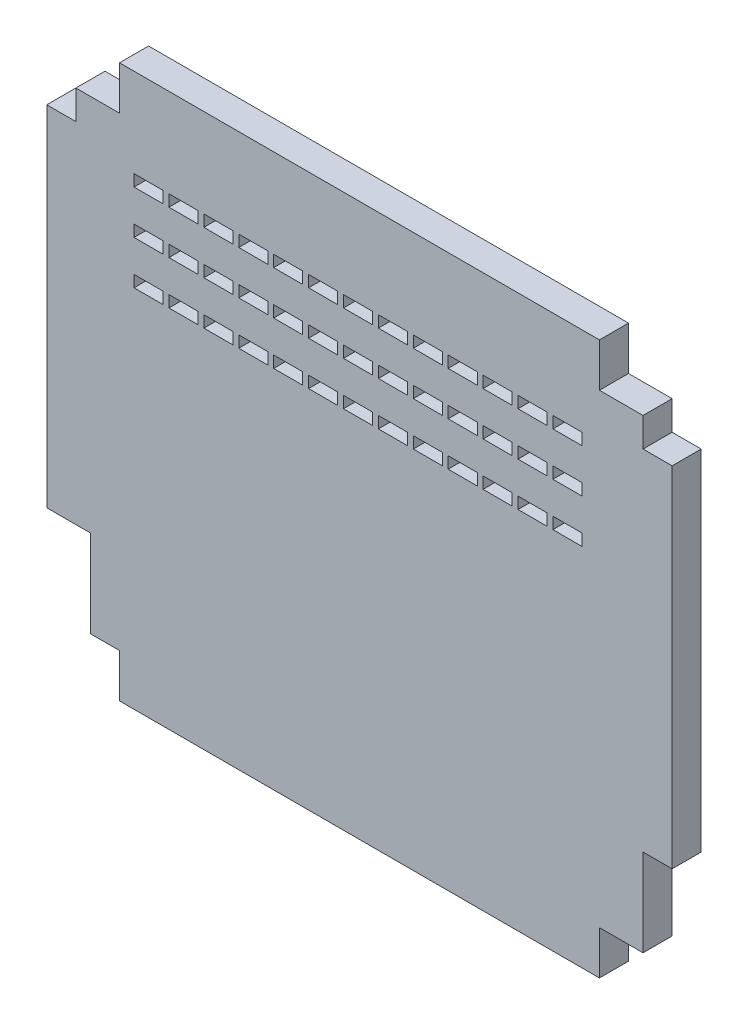
SolidWorks part; units mm, degrees
ref_plane "前视基准面" through (0, 0, 0) normal (0, 0, 1) x (1, 0, 0)
ref_plane "上视基准面" through (0, 0, 0) normal (0, 1, 0) x (1, 0, 0)
ref_plane "右视基准面" through (0, 0, 0) normal (1, 0, 0) x (0, 0, -1)
sketch "草图1" plane through (0, 0, 0) normal (0, 0, 1) x (1, 0, 0)
  line L0 (-82.5, 0) -> (82.5, 0)
  line L2 (107.5, -25) -> (107.5, -145)
  line L3 (-107.5, -25) -> (-107.5, -145)
  line L6 (-82.5, -190) -> (82.5, -190)
  line L8 (-107.5, -25) -> (-97.5, -25)
  line L9 (-97.5, -25) -> (-97.5, -15)
  line L10 (-97.5, -15) -> (-82.5, -15)
  line L11 (-82.5, -15) -> (-82.5, 0)
  line L12 (82.5, 0) -> (82.5, -15)
  line L13 (82.5, -15) -> (97.5, -15)
  line L14 (97.5, -15) -> (97.5, -25)
  line L15 (97.5, -25) -> (107.5, -25)
  line L16 (-107.5, -145) -> (-92.5, -145)
  line L17 (-92.5, -145) -> (-92.5, -175)
  line L18 (-92.5, -175) -> (-82.5, -175)
  line L19 (-82.5, -175) -> (-82.5, -190)
  line L20 (107.5, -145) -> (97.5, -145)
  line L21 (97.5, -145) -> (97.5, -175)
  line L22 (97.5, -175) -> (82.5, -175)
  line L23 (82.5, -175) -> (82.5, -190)
  point P6 (107.5, -85)
  point P9 (-107.5, -85)
  point P11 (0, 0)
  dimension "D1" = 215
  dimension "D2" = 10
  dimension "D3" = 15
  dimension "15" = 15
  dimension "D5" = 10
  dimension "D6" = 15
  dimension "D7" = 15
  dimension "D8" = 120
  dimension "D9" = 30
  dimension "D10" = 30
  dimension "D11" = 15
  dimension "D12" = 10
  dimension "D13" = 15
  dimension "D14" = 10
extrude "凸台-拉伸1" add sketch "草图1" along normal blind 10
sketch "草图2" plane through (0, 0, 0) normal (0, 0, -1) x (-1, 0, 0)
  line L0 (82.5, 0) -> (82.5, -15) construction
  line L161 (-54.5, -5) -> (-54.5, -15)
  line L166 (-54.5, -5) -> (-64.5, -5)
  line L167 (77.5, -5) -> (67.5, -5)
  line L168 (77.5, -5) -> (77.5, -15)
  line L169 (77.5, -15) -> (67.5, -15)
  line L170 (67.5, -5) -> (67.5, -15)
  line L171 (-82.5, 0) -> (82.5, 0) construction
  line L172 (65.5, -5) -> (65.5, -15)
  line L173 (65.5, -5) -> (55.5, -5)
  line L174 (55.5, -5) -> (55.5, -15)
  line L175 (65.5, -15) -> (55.5, -15)
  line L176 (53.5, -5) -> (53.5, -15)
  line L177 (53.5, -5) -> (43.5, -5)
  line L178 (43.5, -5) -> (43.5, -15)
  line L433 (53.5, -15) -> (43.5, -15)
  line L506 (89.5, -20) -> (89.5, -30)
  line L507 (89.5, -30) -> (79.5, -30)
  line L508 (79.5, -20) -> (79.5, -30)
  line L509 (89.5, -20) -> (79.5, -20)
  line L510 (89.5, -35) -> (89.5, -45)
  line L511 (89.5, -45) -> (79.5, -45)
  line L512 (79.5, -35) -> (79.5, -45)
  line L513 (89.5, -35) -> (79.5, -35)
  line L514 (89.5, -50) -> (89.5, -60)
  line L515 (89.5, -60) -> (79.5, -60)
  line L516 (79.5, -50) -> (79.5, -60)
  line L517 (89.5, -50) -> (79.5, -50)
  line L518 (89.5, -65) -> (89.5, -75)
  line L519 (89.5, -75) -> (79.5, -75)
  line L520 (41.5, -5) -> (41.5, -15)
  line L521 (41.5, -5) -> (31.5, -5)
  line L522 (31.5, -5) -> (31.5, -15)
  line L523 (41.5, -15) -> (31.5, -15)
  line L524 (29.5, -5) -> (29.5, -15)
  line L525 (29.5, -5) -> (19.5, -5)
  line L526 (19.5, -5) -> (19.5, -15)
  line L527 (29.5, -15) -> (19.5, -15)
  line L528 (17.5, -5) -> (17.5, -15)
  line L529 (17.5, -5) -> (7.5, -5)
  line L530 (7.5, -5) -> (7.5, -15)
  line L531 (17.5, -15) -> (7.5, -15)
  line L532 (5.5, -5) -> (5.5, -15)
  line L533 (5.5, -5) -> (-4.5, -5)
  line L534 (-4.5, -5) -> (-4.5, -15)
  line L535 (5.5, -15) -> (-4.5, -15)
  line L536 (-6.5, -5) -> (-6.5, -15)
  line L537 (-6.5, -5) -> (-16.5, -5)
  line L538 (-16.5, -5) -> (-16.5, -15)
  line L539 (-6.5, -15) -> (-16.5, -15)
  line L540 (-18.5, -5) -> (-18.5, -15)
  line L541 (-18.5, -5) -> (-28.5, -5)
  line L542 (-28.5, -5) -> (-28.5, -15)
  line L543 (-18.5, -15) -> (-28.5, -15)
  line L544 (-30.5, -5) -> (-30.5, -15)
  line L545 (-30.5, -5) -> (-40.5, -5)
  line L546 (-40.5, -5) -> (-40.5, -15)
  line L547 (-30.5, -15) -> (-40.5, -15)
  line L548 (-42.5, -5) -> (-42.5, -15)
  line L549 (-42.5, -5) -> (-52.5, -5)
  line L550 (-52.5, -5) -> (-52.5, -15)
  line L551 (-42.5, -15) -> (-52.5, -15)
  line L552 (65.5, -20) -> (65.5, -30)
  line L553 (65.5, -20) -> (55.5, -20)
  line L554 (55.5, -20) -> (55.5, -30)
  line L555 (65.5, -30) -> (55.5, -30)
  line L556 (53.5, -20) -> (53.5, -30)
  line L557 (53.5, -20) -> (43.5, -20)
  line L558 (43.5, -20) -> (43.5, -30)
  line L559 (53.5, -30) -> (43.5, -30)
  line L560 (41.5, -20) -> (41.5, -30)
  line L561 (41.5, -20) -> (31.5, -20)
  line L562 (31.5, -20) -> (31.5, -30)
  line L563 (41.5, -30) -> (31.5, -30)
  line L564 (29.5, -20) -> (29.5, -30)
  line L565 (29.5, -20) -> (19.5, -20)
  line L566 (19.5, -20) -> (19.5, -30)
  line L567 (29.5, -30) -> (19.5, -30)
  line L568 (17.5, -20) -> (17.5, -30)
  line L569 (17.5, -20) -> (7.5, -20)
  line L570 (7.5, -20) -> (7.5, -30)
  line L571 (17.5, -30) -> (7.5, -30)
  line L572 (5.5, -20) -> (5.5, -30)
  line L573 (5.5, -20) -> (-4.5, -20)
  line L574 (-4.5, -20) -> (-4.5, -30)
  line L575 (5.5, -30) -> (-4.5, -30)
  line L576 (-6.5, -20) -> (-6.5, -30)
  line L577 (-6.5, -20) -> (-16.5, -20)
  line L578 (-16.5, -20) -> (-16.5, -30)
  line L579 (-6.5, -30) -> (-16.5, -30)
  line L580 (-18.5, -20) -> (-18.5, -30)
  line L581 (-18.5, -20) -> (-28.5, -20)
  line L582 (-28.5, -20) -> (-28.5, -30)
  line L583 (-18.5, -30) -> (-28.5, -30)
  line L584 (-30.5, -20) -> (-30.5, -30)
  line L585 (-30.5, -20) -> (-40.5, -20)
  line L586 (-40.5, -20) -> (-40.5, -30)
  line L587 (-30.5, -30) -> (-40.5, -30)
  line L588 (-42.5, -20) -> (-42.5, -30)
  line L589 (-42.5, -20) -> (-52.5, -20)
  line L590 (-52.5, -20) -> (-52.5, -30)
  line L591 (-42.5, -30) -> (-52.5, -30)
  line L592 (65.5, -35) -> (65.5, -45)
  line L593 (65.5, -35) -> (55.5, -35)
  line L594 (55.5, -35) -> (55.5, -45)
  line L595 (65.5, -45) -> (55.5, -45)
  line L596 (53.5, -35) -> (53.5, -45)
  line L597 (53.5, -35) -> (43.5, -35)
  line L598 (43.5, -35) -> (43.5, -45)
  line L599 (53.5, -45) -> (43.5, -45)
  line L600 (41.5, -35) -> (41.5, -45)
  line L601 (41.5, -35) -> (31.5, -35)
  line L602 (31.5, -35) -> (31.5, -45)
  line L603 (41.5, -45) -> (31.5, -45)
  line L604 (29.5, -35) -> (29.5, -45)
  line L605 (29.5, -35) -> (19.5, -35)
  line L606 (19.5, -35) -> (19.5, -45)
  line L607 (29.5, -45) -> (19.5, -45)
  line L608 (17.5, -35) -> (17.5, -45)
  line L609 (17.5, -35) -> (7.5, -35)
  line L610 (7.5, -35) -> (7.5, -45)
  line L611 (17.5, -45) -> (7.5, -45)
  line L612 (5.5, -35) -> (5.5, -45)
  line L613 (5.5, -35) -> (-4.5, -35)
  line L614 (-4.5, -35) -> (-4.5, -45)
  line L615 (5.5, -45) -> (-4.5, -45)
  line L616 (-6.5, -35) -> (-6.5, -45)
  line L617 (-6.5, -35) -> (-16.5, -35)
  line L618 (-16.5, -35) -> (-16.5, -45)
  line L619 (-6.5, -45) -> (-16.5, -45)
  line L620 (-18.5, -35) -> (-18.5, -45)
  line L621 (-18.5, -35) -> (-28.5, -35)
  line L622 (-28.5, -35) -> (-28.5, -45)
  line L623 (-18.5, -45) -> (-28.5, -45)
  line L624 (-30.5, -35) -> (-30.5, -45)
  line L625 (-30.5, -35) -> (-40.5, -35)
  line L626 (-40.5, -35) -> (-40.5, -45)
  line L627 (-30.5, -45) -> (-40.5, -45)
  line L628 (-42.5, -35) -> (-42.5, -45)
  line L629 (-42.5, -35) -> (-52.5, -35)
  line L630 (-52.5, -35) -> (-52.5, -45)
  line L631 (-42.5, -45) -> (-52.5, -45)
  line L632 (65.5, -50) -> (65.5, -60)
  line L633 (65.5, -50) -> (55.5, -50)
  line L634 (55.5, -50) -> (55.5, -60)
  line L635 (65.5, -60) -> (55.5, -60)
  line L636 (53.5, -50) -> (53.5, -60)
  line L637 (53.5, -50) -> (43.5, -50)
  line L638 (43.5, -50) -> (43.5, -60)
  line L639 (53.5, -60) -> (43.5, -60)
  line L640 (41.5, -50) -> (41.5, -60)
  line L641 (41.5, -50) -> (31.5, -50)
  line L642 (31.5, -50) -> (31.5, -60)
  line L643 (41.5, -60) -> (31.5, -60)
  line L644 (29.5, -50) -> (29.5, -60)
  line L645 (29.5, -50) -> (19.5, -50)
  line L646 (19.5, -50) -> (19.5, -60)
  line L647 (29.5, -60) -> (19.5, -60)
  line L648 (17.5, -50) -> (17.5, -60)
  line L649 (17.5, -50) -> (7.5, -50)
  line L650 (7.5, -50) -> (7.5, -60)
  line L651 (17.5, -60) -> (7.5, -60)
  line L652 (5.5, -50) -> (5.5, -60)
  line L653 (5.5, -50) -> (-4.5, -50)
  line L654 (-4.5, -50) -> (-4.5, -60)
  line L655 (5.5, -60) -> (-4.5, -60)
  line L656 (-6.5, -50) -> (-6.5, -60)
  line L657 (-6.5, -50) -> (-16.5, -50)
  line L658 (-16.5, -50) -> (-16.5, -60)
  line L659 (-6.5, -60) -> (-16.5, -60)
  line L660 (-18.5, -50) -> (-18.5, -60)
  line L661 (-18.5, -50) -> (-28.5, -50)
  line L662 (-28.5, -50) -> (-28.5, -60)
  line L663 (-18.5, -60) -> (-28.5, -60)
  line L664 (-30.5, -50) -> (-30.5, -60)
  line L665 (-30.5, -50) -> (-40.5, -50)
  line L666 (-40.5, -50) -> (-40.5, -60)
  line L667 (-30.5, -60) -> (-40.5, -60)
  line L668 (-42.5, -50) -> (-42.5, -60)
  line L669 (-42.5, -50) -> (-52.5, -50)
  line L670 (-52.5, -50) -> (-52.5, -60)
  line L671 (-42.5, -60) -> (-52.5, -60)
  line L672 (65.5, -65) -> (65.5, -75)
  line L673 (65.5, -65) -> (55.5, -65)
  line L674 (55.5, -65) -> (55.5, -75)
  line L675 (65.5, -75) -> (55.5, -75)
  line L676 (53.5, -65) -> (53.5, -75)
  line L677 (53.5, -65) -> (43.5, -65)
  line L678 (43.5, -65) -> (43.5, -75)
  line L679 (53.5, -75) -> (43.5, -75)
  line L680 (41.5, -65) -> (41.5, -75)
  line L681 (41.5, -65) -> (31.5, -65)
  line L682 (31.5, -65) -> (31.5, -75)
  line L683 (41.5, -75) -> (31.5, -75)
  line L684 (29.5, -65) -> (29.5, -75)
  line L685 (29.5, -65) -> (19.5, -65)
  line L686 (19.5, -65) -> (19.5, -75)
  line L687 (29.5, -75) -> (19.5, -75)
  line L688 (17.5, -65) -> (17.5, -75)
  line L689 (17.5, -65) -> (7.5, -65)
  line L690 (7.5, -65) -> (7.5, -75)
  line L691 (17.5, -75) -> (7.5, -75)
  line L692 (5.5, -65) -> (5.5, -75)
  line L693 (5.5, -65) -> (-4.5, -65)
  line L694 (-4.5, -65) -> (-4.5, -75)
  line L695 (5.5, -75) -> (-4.5, -75)
  line L696 (-6.5, -65) -> (-6.5, -75)
  line L697 (-6.5, -65) -> (-16.5, -65)
  line L698 (-16.5, -65) -> (-16.5, -75)
  line L699 (-6.5, -75) -> (-16.5, -75)
  line L700 (-18.5, -65) -> (-18.5, -75)
  line L701 (-18.5, -65) -> (-28.5, -65)
  line L702 (-28.5, -65) -> (-28.5, -75)
  line L703 (-18.5, -75) -> (-28.5, -75)
  line L704 (-30.5, -65) -> (-30.5, -75)
  line L705 (-30.5, -65) -> (-40.5, -65)
  line L706 (-40.5, -65) -> (-40.5, -75)
  line L707 (-30.5, -75) -> (-40.5, -75)
  line L708 (-42.5, -65) -> (-42.5, -75)
  line L709 (-42.5, -65) -> (-52.5, -65)
  line L710 (-52.5, -65) -> (-52.5, -75)
  line L711 (-42.5, -75) -> (-52.5, -75)
  line L712 (65.5, -80) -> (65.5, -90)
  line L713 (65.5, -80) -> (55.5, -80)
  line L714 (55.5, -80) -> (55.5, -90)
  line L715 (65.5, -90) -> (55.5, -90)
  line L716 (53.5, -80) -> (53.5, -90)
  line L717 (53.5, -80) -> (43.5, -80)
  line L718 (43.5, -80) -> (43.5, -90)
  line L719 (53.5, -90) -> (43.5, -90)
  line L720 (41.5, -80) -> (41.5, -90)
  line L721 (41.5, -80) -> (31.5, -80)
  line L722 (31.5, -80) -> (31.5, -90)
  line L723 (41.5, -90) -> (31.5, -90)
  line L724 (29.5, -80) -> (29.5, -90)
  line L725 (29.5, -80) -> (19.5, -80)
  line L726 (19.5, -80) -> (19.5, -90)
  line L727 (29.5, -90) -> (19.5, -90)
  line L728 (17.5, -80) -> (17.5, -90)
  line L729 (17.5, -80) -> (7.5, -80)
  line L730 (7.5, -80) -> (7.5, -90)
  line L731 (17.5, -90) -> (7.5, -90)
  line L732 (5.5, -80) -> (5.5, -90)
  line L733 (5.5, -80) -> (-4.5, -80)
  line L734 (-4.5, -80) -> (-4.5, -90)
  line L735 (5.5, -90) -> (-4.5, -90)
  line L736 (-6.5, -80) -> (-6.5, -90)
  line L737 (-6.5, -80) -> (-16.5, -80)
  line L738 (-16.5, -80) -> (-16.5, -90)
  line L739 (-6.5, -90) -> (-16.5, -90)
  line L740 (-18.5, -80) -> (-18.5, -90)
  line L741 (-18.5, -80) -> (-28.5, -80)
  line L742 (-28.5, -80) -> (-28.5, -90)
  line L743 (-18.5, -90) -> (-28.5, -90)
  line L744 (-30.5, -80) -> (-30.5, -90)
  line L745 (-30.5, -80) -> (-40.5, -80)
  line L746 (-40.5, -80) -> (-40.5, -90)
  line L747 (-30.5, -90) -> (-40.5, -90)
  line L748 (-42.5, -80) -> (-42.5, -90)
  line L749 (-42.5, -80) -> (-52.5, -80)
  line L750 (-52.5, -80) -> (-52.5, -90)
  line L751 (-42.5, -90) -> (-52.5, -90)
  line L752 (65.5, -95) -> (65.5, -105)
  line L753 (65.5, -95) -> (55.5, -95)
  line L754 (55.5, -95) -> (55.5, -105)
  line L755 (65.5, -105) -> (55.5, -105)
  line L756 (53.5, -95) -> (53.5, -105)
  line L757 (53.5, -95) -> (43.5, -95)
  line L758 (43.5, -95) -> (43.5, -105)
  line L759 (53.5, -105) -> (43.5, -105)
  line L760 (41.5, -95) -> (41.5, -105)
  line L761 (41.5, -95) -> (31.5, -95)
  line L762 (31.5, -95) -> (31.5, -105)
  line L763 (41.5, -105) -> (31.5, -105)
  line L764 (29.5, -95) -> (29.5, -105)
  line L765 (29.5, -95) -> (19.5, -95)
  line L766 (19.5, -95) -> (19.5, -105)
  line L767 (29.5, -105) -> (19.5, -105)
  line L768 (17.5, -95) -> (17.5, -105)
  line L769 (17.5, -95) -> (7.5, -95)
  line L770 (7.5, -95) -> (7.5, -105)
  line L771 (17.5, -105) -> (7.5, -105)
  line L772 (5.5, -95) -> (5.5, -105)
  line L773 (5.5, -95) -> (-4.5, -95)
  line L774 (-4.5, -95) -> (-4.5, -105)
  line L775 (5.5, -105) -> (-4.5, -105)
  line L776 (-6.5, -95) -> (-6.5, -105)
  line L777 (-6.5, -95) -> (-16.5, -95)
  line L778 (-16.5, -95) -> (-16.5, -105)
  line L779 (-6.5, -105) -> (-16.5, -105)
  line L780 (-18.5, -95) -> (-18.5, -105)
  line L781 (-18.5, -95) -> (-28.5, -95)
  line L782 (-28.5, -95) -> (-28.5, -105)
  line L783 (-18.5, -105) -> (-28.5, -105)
  line L784 (-30.5, -95) -> (-30.5, -105)
  line L785 (-30.5, -95) -> (-40.5, -95)
  line L786 (-40.5, -95) -> (-40.5, -105)
  line L787 (-30.5, -105) -> (-40.5, -105)
  line L788 (-42.5, -95) -> (-42.5, -105)
  line L789 (-42.5, -95) -> (-52.5, -95)
  line L790 (-52.5, -95) -> (-52.5, -105)
  line L791 (-42.5, -105) -> (-52.5, -105)
  line L792 (65.5, -110) -> (65.5, -120)
  line L793 (65.5, -110) -> (55.5, -110)
  line L794 (55.5, -110) -> (55.5, -120)
  line L795 (65.5, -120) -> (55.5, -120)
  line L796 (53.5, -110) -> (53.5, -120)
  line L797 (53.5, -110) -> (43.5, -110)
  line L798 (43.5, -110) -> (43.5, -120)
  line L799 (53.5, -120) -> (43.5, -120)
  line L800 (41.5, -110) -> (41.5, -120)
  line L801 (41.5, -110) -> (31.5, -110)
  line L802 (31.5, -110) -> (31.5, -120)
  line L803 (41.5, -120) -> (31.5, -120)
  line L804 (29.5, -110) -> (29.5, -120)
  line L805 (29.5, -110) -> (19.5, -110)
  line L806 (19.5, -110) -> (19.5, -120)
  line L807 (29.5, -120) -> (19.5, -120)
  line L808 (17.5, -110) -> (17.5, -120)
  line L809 (17.5, -110) -> (7.5, -110)
  line L810 (7.5, -110) -> (7.5, -120)
  line L811 (17.5, -120) -> (7.5, -120)
  line L812 (5.5, -110) -> (5.5, -120)
  line L813 (5.5, -110) -> (-4.5, -110)
  line L814 (-4.5, -110) -> (-4.5, -120)
  line L815 (5.5, -120) -> (-4.5, -120)
  line L816 (-6.5, -110) -> (-6.5, -120)
  line L817 (-6.5, -110) -> (-16.5, -110)
  line L818 (-16.5, -110) -> (-16.5, -120)
  line L819 (-6.5, -120) -> (-16.5, -120)
  line L820 (-18.5, -110) -> (-18.5, -120)
  line L821 (-18.5, -110) -> (-28.5, -110)
  line L822 (-28.5, -110) -> (-28.5, -120)
  line L823 (-18.5, -120) -> (-28.5, -120)
  line L824 (-30.5, -110) -> (-30.5, -120)
  line L825 (-30.5, -110) -> (-40.5, -110)
  line L826 (-40.5, -110) -> (-40.5, -120)
  line L827 (-30.5, -120) -> (-40.5, -120)
  line L828 (-42.5, -110) -> (-42.5, -120)
  line L829 (-42.5, -110) -> (-52.5, -110)
  line L830 (-52.5, -110) -> (-52.5, -120)
  line L831 (-42.5, -120) -> (-52.5, -120)
  line L832 (65.5, -125) -> (65.5, -135)
  line L833 (65.5, -125) -> (55.5, -125)
  line L834 (55.5, -125) -> (55.5, -135)
  line L835 (65.5, -135) -> (55.5, -135)
  line L836 (53.5, -125) -> (53.5, -135)
  line L837 (53.5, -125) -> (43.5, -125)
  line L838 (43.5, -125) -> (43.5, -135)
  line L839 (53.5, -135) -> (43.5, -135)
  line L840 (41.5, -125) -> (41.5, -135)
  line L841 (41.5, -125) -> (31.5, -125)
  line L842 (31.5, -125) -> (31.5, -135)
  line L843 (41.5, -135) -> (31.5, -135)
  line L844 (29.5, -125) -> (29.5, -135)
  line L845 (29.5, -125) -> (19.5, -125)
  line L846 (19.5, -125) -> (19.5, -135)
  line L847 (29.5, -135) -> (19.5, -135)
  line L848 (17.5, -125) -> (17.5, -135)
  line L849 (17.5, -125) -> (7.5, -125)
  line L850 (7.5, -125) -> (7.5, -135)
  line L851 (17.5, -135) -> (7.5, -135)
  line L852 (5.5, -125) -> (5.5, -135)
  line L853 (5.5, -125) -> (-4.5, -125)
  line L854 (-4.5, -125) -> (-4.5, -135)
  line L855 (5.5, -135) -> (-4.5, -135)
  line L856 (-6.5, -125) -> (-6.5, -135)
  line L857 (-6.5, -125) -> (-16.5, -125)
  line L858 (-16.5, -125) -> (-16.5, -135)
  line L859 (-6.5, -135) -> (-16.5, -135)
  line L860 (-18.5, -125) -> (-18.5, -135)
  line L861 (-18.5, -125) -> (-28.5, -125)
  line L862 (-28.5, -125) -> (-28.5, -135)
  line L863 (-18.5, -135) -> (-28.5, -135)
  line L864 (-30.5, -125) -> (-30.5, -135)
  line L865 (-30.5, -125) -> (-40.5, -125)
  line L866 (-40.5, -125) -> (-40.5, -135)
  line L867 (-30.5, -135) -> (-40.5, -135)
  line L868 (-42.5, -125) -> (-42.5, -135)
  line L869 (-42.5, -125) -> (-52.5, -125)
  line L870 (-52.5, -125) -> (-52.5, -135)
  line L871 (-42.5, -135) -> (-52.5, -135)
  line L872 (65.5, -140) -> (65.5, -150)
  line L873 (65.5, -140) -> (55.5, -140)
  line L874 (55.5, -140) -> (55.5, -150)
  line L875 (65.5, -150) -> (55.5, -150)
  line L876 (53.5, -140) -> (53.5, -150)
  line L877 (53.5, -140) -> (43.5, -140)
  line L878 (43.5, -140) -> (43.5, -150)
  line L879 (53.5, -150) -> (43.5, -150)
  line L880 (41.5, -140) -> (41.5, -150)
  line L881 (41.5, -140) -> (31.5, -140)
  line L882 (31.5, -140) -> (31.5, -150)
  line L883 (41.5, -150) -> (31.5, -150)
  line L884 (29.5, -140) -> (29.5, -150)
  line L885 (29.5, -140) -> (19.5, -140)
  line L886 (19.5, -140) -> (19.5, -150)
  line L887 (29.5, -150) -> (19.5, -150)
  line L888 (17.5, -140) -> (17.5, -150)
  line L889 (17.5, -140) -> (7.5, -140)
  line L890 (7.5, -140) -> (7.5, -150)
  line L891 (17.5, -150) -> (7.5, -150)
  line L892 (5.5, -140) -> (5.5, -150)
  line L893 (5.5, -140) -> (-4.5, -140)
  line L894 (-4.5, -140) -> (-4.5, -150)
  line L895 (5.5, -150) -> (-4.5, -150)
  line L896 (-6.5, -140) -> (-6.5, -150)
  line L897 (-6.5, -140) -> (-16.5, -140)
  line L898 (-16.5, -140) -> (-16.5, -150)
  line L899 (-6.5, -150) -> (-16.5, -150)
  line L900 (-18.5, -140) -> (-18.5, -150)
  line L901 (-18.5, -140) -> (-28.5, -140)
  line L902 (-28.5, -140) -> (-28.5, -150)
  line L903 (-18.5, -150) -> (-28.5, -150)
  line L904 (-30.5, -140) -> (-30.5, -150)
  line L905 (-30.5, -140) -> (-40.5, -140)
  line L906 (-40.5, -140) -> (-40.5, -150)
  line L907 (-30.5, -150) -> (-40.5, -150)
  line L908 (-42.5, -140) -> (-42.5, -150)
  line L909 (-42.5, -140) -> (-52.5, -140)
  line L910 (-52.5, -140) -> (-52.5, -150)
  line L911 (-42.5, -150) -> (-52.5, -150)
  line L912 (65.5, -155) -> (65.5, -165)
  line L913 (65.5, -155) -> (55.5, -155)
  line L914 (55.5, -155) -> (55.5, -165)
  line L915 (65.5, -165) -> (55.5, -165)
  line L916 (53.5, -155) -> (53.5, -165)
  line L917 (53.5, -155) -> (43.5, -155)
  line L918 (43.5, -155) -> (43.5, -165)
  line L919 (53.5, -165) -> (43.5, -165)
  line L920 (41.5, -155) -> (41.5, -165)
  line L921 (41.5, -155) -> (31.5, -155)
  line L922 (31.5, -155) -> (31.5, -165)
  line L923 (41.5, -165) -> (31.5, -165)
  line L924 (29.5, -155) -> (29.5, -165)
  line L925 (29.5, -155) -> (19.5, -155)
  line L926 (19.5, -155) -> (19.5, -165)
  line L927 (29.5, -165) -> (19.5, -165)
  line L928 (17.5, -155) -> (17.5, -165)
  line L929 (17.5, -155) -> (7.5, -155)
  line L930 (7.5, -155) -> (7.5, -165)
  line L931 (17.5, -165) -> (7.5, -165)
  line L932 (5.5, -155) -> (5.5, -165)
  line L933 (5.5, -155) -> (-4.5, -155)
  line L934 (-4.5, -155) -> (-4.5, -165)
  line L935 (5.5, -165) -> (-4.5, -165)
  line L936 (-6.5, -155) -> (-6.5, -165)
  line L937 (-6.5, -155) -> (-16.5, -155)
  line L938 (-16.5, -155) -> (-16.5, -165)
  line L939 (-6.5, -165) -> (-16.5, -165)
  line L940 (-18.5, -155) -> (-18.5, -165)
  line L941 (-18.5, -155) -> (-28.5, -155)
  line L942 (-28.5, -155) -> (-28.5, -165)
  line L943 (-18.5, -165) -> (-28.5, -165)
  line L944 (-30.5, -155) -> (-30.5, -165)
  line L945 (-30.5, -155) -> (-40.5, -155)
  line L946 (-40.5, -155) -> (-40.5, -165)
  line L947 (-30.5, -165) -> (-40.5, -165)
  line L948 (-42.5, -155) -> (-42.5, -165)
  line L949 (-42.5, -155) -> (-52.5, -155)
  line L950 (-52.5, -155) -> (-52.5, -165)
  line L951 (-42.5, -165) -> (-52.5, -165)
  line L952 (65.5, -170) -> (65.5, -180)
  line L953 (65.5, -170) -> (55.5, -170)
  line L954 (55.5, -170) -> (55.5, -180)
  line L955 (65.5, -180) -> (55.5, -180)
  line L956 (53.5, -170) -> (53.5, -180)
  line L957 (53.5, -170) -> (43.5, -170)
  line L958 (43.5, -170) -> (43.5, -180)
  line L959 (53.5, -180) -> (43.5, -180)
  line L960 (41.5, -170) -> (41.5, -180)
  line L961 (41.5, -170) -> (31.5, -170)
  line L962 (31.5, -170) -> (31.5, -180)
  line L963 (41.5, -180) -> (31.5, -180)
  line L964 (29.5, -170) -> (29.5, -180)
  line L965 (29.5, -170) -> (19.5, -170)
  line L966 (19.5, -170) -> (19.5, -180)
  line L967 (29.5, -180) -> (19.5, -180)
  line L968 (17.5, -170) -> (17.5, -180)
  line L969 (17.5, -170) -> (7.5, -170)
  line L970 (7.5, -170) -> (7.5, -180)
  line L971 (17.5, -180) -> (7.5, -180)
  line L972 (5.5, -170) -> (5.5, -180)
  line L973 (5.5, -170) -> (-4.5, -170)
  line L974 (-4.5, -170) -> (-4.5, -180)
  line L975 (5.5, -180) -> (-4.5, -180)
  line L976 (-6.5, -170) -> (-6.5, -180)
  line L977 (-6.5, -170) -> (-16.5, -170)
  line L978 (-16.5, -170) -> (-16.5, -180)
  line L979 (-6.5, -180) -> (-16.5, -180)
  line L980 (-18.5, -170) -> (-18.5, -180)
  line L981 (-18.5, -170) -> (-28.5, -170)
  line L982 (-28.5, -170) -> (-28.5, -180)
  line L983 (-18.5, -180) -> (-28.5, -180)
  line L984 (-30.5, -170) -> (-30.5, -180)
  line L985 (-30.5, -170) -> (-40.5, -170)
  line L986 (-40.5, -170) -> (-40.5, -180)
  line L987 (-30.5, -180) -> (-40.5, -180)
  line L988 (-42.5, -170) -> (-42.5, -180)
  line L989 (-42.5, -170) -> (-52.5, -170)
  line L990 (-52.5, -170) -> (-52.5, -180)
  line L991 (-42.5, -180) -> (-52.5, -180)
  line L992 (77.5, -20) -> (77.5, -30)
  line L993 (77.5, -20) -> (67.5, -20)
  line L994 (67.5, -20) -> (67.5, -30)
  line L995 (77.5, -30) -> (67.5, -30)
  line L996 (77.5, -35) -> (77.5, -45)
  line L997 (77.5, -35) -> (67.5, -35)
  line L998 (67.5, -35) -> (67.5, -45)
  line L999 (77.5, -45) -> (67.5, -45)
  line L1000 (77.5, -50) -> (77.5, -60)
  line L1001 (77.5, -50) -> (67.5, -50)
  line L1002 (67.5, -50) -> (67.5, -60)
  line L1003 (77.5, -60) -> (67.5, -60)
  line L1004 (77.5, -65) -> (77.5, -75)
  line L1005 (77.5, -65) -> (67.5, -65)
  line L1006 (67.5, -65) -> (67.5, -75)
  line L1007 (77.5, -75) -> (67.5, -75)
  line L1008 (77.5, -80) -> (77.5, -90)
  line L1009 (77.5, -80) -> (67.5, -80)
  line L1010 (67.5, -80) -> (67.5, -90)
  line L1011 (77.5, -90) -> (67.5, -90)
  line L1012 (77.5, -95) -> (77.5, -105)
  line L1013 (77.5, -95) -> (67.5, -95)
  line L1014 (67.5, -95) -> (67.5, -105)
  line L1015 (77.5, -105) -> (67.5, -105)
  line L1016 (77.5, -110) -> (77.5, -120)
  line L1017 (77.5, -110) -> (67.5, -110)
  line L1018 (67.5, -110) -> (67.5, -120)
  line L1019 (77.5, -120) -> (67.5, -120)
  line L1020 (77.5, -125) -> (77.5, -135)
  line L1021 (77.5, -125) -> (67.5, -125)
  line L1022 (67.5, -125) -> (67.5, -135)
  line L1023 (77.5, -135) -> (67.5, -135)
  line L1024 (77.5, -140) -> (77.5, -150)
  line L1025 (77.5, -140) -> (67.5, -140)
  line L1026 (67.5, -140) -> (67.5, -150)
  line L1027 (77.5, -150) -> (67.5, -150)
  line L1028 (77.5, -155) -> (77.5, -165)
  line L1029 (77.5, -155) -> (67.5, -155)
  line L1030 (67.5, -155) -> (67.5, -165)
  line L1031 (77.5, -165) -> (67.5, -165)
  line L1032 (77.5, -170) -> (77.5, -180)
  line L1033 (77.5, -170) -> (67.5, -170)
  line L1034 (67.5, -170) -> (67.5, -180)
  line L1035 (77.5, -180) -> (67.5, -180)
  line L1036 (79.5, -65) -> (79.5, -75)
  line L1037 (89.5, -65) -> (79.5, -65)
  line L1038 (89.5, -80) -> (89.5, -90)
  line L1039 (89.5, -90) -> (79.5, -90)
  line L1040 (79.5, -80) -> (79.5, -90)
  line L1041 (89.5, -80) -> (79.5, -80)
  line L1042 (89.5, -95) -> (89.5, -105)
  line L1043 (89.5, -105) -> (79.5, -105)
  line L1044 (79.5, -95) -> (79.5, -105)
  line L1045 (89.5, -95) -> (79.5, -95)
  line L1046 (89.5, -110) -> (89.5, -120)
  line L1047 (89.5, -120) -> (79.5, -120)
  line L1048 (79.5, -110) -> (79.5, -120)
  line L1049 (89.5, -110) -> (79.5, -110)
  line L1050 (89.5, -125) -> (89.5, -135)
  line L1051 (89.5, -135) -> (79.5, -135)
  line L1052 (79.5, -125) -> (79.5, -135)
  line L1053 (89.5, -125) -> (79.5, -125)
  line L1054 (-54.5, -20) -> (-54.5, -30)
  line L1055 (-54.5, -30) -> (-64.5, -30)
  line L1056 (-64.5, -20) -> (-64.5, -30)
  line L1057 (-54.5, -20) -> (-64.5, -20)
  line L1058 (-54.5, -35) -> (-54.5, -45)
  line L1059 (-54.5, -45) -> (-64.5, -45)
  line L1060 (-64.5, -35) -> (-64.5, -45)
  line L1061 (-54.5, -35) -> (-64.5, -35)
  line L1062 (-54.5, -50) -> (-54.5, -60)
  line L1063 (-54.5, -60) -> (-64.5, -60)
  line L1064 (-64.5, -50) -> (-64.5, -60)
  line L1065 (-54.5, -50) -> (-64.5, -50)
  line L1066 (-54.5, -65) -> (-54.5, -75)
  line L1067 (-54.5, -75) -> (-64.5, -75)
  line L1068 (-64.5, -65) -> (-64.5, -75)
  line L1069 (-54.5, -65) -> (-64.5, -65)
  line L1070 (-54.5, -80) -> (-54.5, -90)
  line L1071 (-54.5, -90) -> (-64.5, -90)
  line L1072 (-64.5, -80) -> (-64.5, -90)
  line L1073 (-54.5, -80) -> (-64.5, -80)
  line L1074 (-54.5, -95) -> (-54.5, -105)
  line L1075 (-54.5, -105) -> (-64.5, -105)
  line L1076 (-64.5, -95) -> (-64.5, -105)
  line L1077 (-54.5, -95) -> (-64.5, -95)
  line L1078 (-54.5, -110) -> (-54.5, -120)
  line L1079 (-54.5, -120) -> (-64.5, -120)
  line L1080 (-64.5, -110) -> (-64.5, -120)
  line L1081 (-54.5, -110) -> (-64.5, -110)
  line L1082 (-54.5, -125) -> (-54.5, -135)
  line L1083 (-54.5, -135) -> (-64.5, -135)
  line L1084 (-64.5, -125) -> (-64.5, -135)
  line L1085 (-54.5, -125) -> (-64.5, -125)
  line L1086 (-64.5, -5) -> (-64.5, -15)
  line L1087 (-54.5, -15) -> (-64.5, -15)
  line L1088 (-66.5, -5) -> (-66.5, -15)
  line L1089 (-66.5, -5) -> (-76.5, -5)
  line L1090 (-76.5, -5) -> (-76.5, -15)
  line L1091 (-66.5, -15) -> (-76.5, -15)
  line L1092 (-66.5, -20) -> (-66.5, -30)
  line L1093 (-66.5, -30) -> (-76.5, -30)
  line L1094 (-76.5, -20) -> (-76.5, -30)
  line L1095 (-66.5, -20) -> (-76.5, -20)
  line L1096 (-66.5, -35) -> (-66.5, -45)
  line L1097 (-66.5, -45) -> (-76.5, -45)
  line L1098 (-76.5, -35) -> (-76.5, -45)
  line L1099 (-66.5, -35) -> (-76.5, -35)
  line L1100 (-66.5, -50) -> (-66.5, -60)
  line L1101 (-66.5, -60) -> (-76.5, -60)
  line L1102 (-76.5, -50) -> (-76.5, -60)
  line L1103 (-66.5, -50) -> (-76.5, -50)
  line L1104 (-66.5, -65) -> (-66.5, -75)
  line L1105 (-66.5, -75) -> (-76.5, -75)
  line L1106 (-76.5, -65) -> (-76.5, -75)
  line L1107 (-66.5, -65) -> (-76.5, -65)
  line L1108 (-66.5, -80) -> (-66.5, -90)
  line L1109 (-66.5, -90) -> (-76.5, -90)
  line L1110 (-76.5, -80) -> (-76.5, -90)
  line L1111 (-66.5, -80) -> (-76.5, -80)
  line L1112 (-66.5, -95) -> (-66.5, -105)
  line L1113 (-66.5, -105) -> (-76.5, -105)
  line L1114 (-76.5, -95) -> (-76.5, -105)
  line L1115 (-66.5, -95) -> (-76.5, -95)
  line L1116 (-66.5, -110) -> (-66.5, -120)
  line L1117 (-66.5, -120) -> (-76.5, -120)
  line L1118 (-76.5, -110) -> (-76.5, -120)
  line L1119 (-66.5, -110) -> (-76.5, -110)
  line L1120 (-66.5, -125) -> (-66.5, -135)
  line L1121 (-66.5, -135) -> (-76.5, -135)
  line L1122 (-76.5, -125) -> (-76.5, -135)
  line L1123 (-66.5, -125) -> (-76.5, -125)
  line L1124 (-78.5, -20) -> (-78.5, -30)
  line L1125 (-78.5, -30) -> (-88.5, -30)
  line L1126 (-88.5, -20) -> (-88.5, -30)
  line L1127 (-78.5, -20) -> (-88.5, -20)
  line L1128 (-78.5, -35) -> (-78.5, -45)
  line L1129 (-78.5, -45) -> (-88.5, -45)
  line L1130 (-88.5, -35) -> (-88.5, -45)
  line L1131 (-78.5, -35) -> (-88.5, -35)
  line L1132 (-78.5, -50) -> (-78.5, -60)
  line L1133 (-78.5, -60) -> (-88.5, -60)
  line L1134 (-88.5, -50) -> (-88.5, -60)
  line L1135 (-78.5, -50) -> (-88.5, -50)
  line L1136 (-78.5, -65) -> (-78.5, -75)
  line L1137 (-78.5, -75) -> (-88.5, -75)
  line L1138 (-88.5, -65) -> (-88.5, -75)
  line L1139 (-78.5, -65) -> (-88.5, -65)
  line L1140 (-78.5, -80) -> (-78.5, -90)
  line L1141 (-78.5, -90) -> (-88.5, -90)
  line L1142 (-88.5, -80) -> (-88.5, -90)
  line L1143 (-78.5, -80) -> (-88.5, -80)
  line L1144 (-78.5, -95) -> (-78.5, -105)
  line L1145 (-78.5, -105) -> (-88.5, -105)
  line L1146 (-88.5, -95) -> (-88.5, -105)
  line L1147 (-78.5, -95) -> (-88.5, -95)
  line L1148 (-78.5, -110) -> (-78.5, -120)
  line L1149 (-78.5, -120) -> (-88.5, -120)
  line L1150 (-88.5, -110) -> (-88.5, -120)
  line L1151 (-78.5, -110) -> (-88.5, -110)
  line L1152 (-78.5, -125) -> (-78.5, -135)
  line L1153 (-78.5, -135) -> (-88.5, -135)
  line L1154 (-88.5, -125) -> (-88.5, -135)
  line L1155 (-78.5, -125) -> (-88.5, -125)
  line L1156 (-54.5, -140) -> (-54.5, -150)
  line L1157 (-54.5, -140) -> (-64.5, -140)
  line L1158 (-64.5, -140) -> (-64.5, -150)
  line L1159 (-54.5, -150) -> (-64.5, -150)
  line L1160 (-54.5, -155) -> (-54.5, -165)
  line L1161 (-54.5, -155) -> (-64.5, -155)
  line L1162 (-64.5, -155) -> (-64.5, -165)
  line L1163 (-54.5, -165) -> (-64.5, -165)
  line L1164 (-54.5, -170) -> (-54.5, -180)
  line L1165 (-54.5, -170) -> (-64.5, -170)
  line L1166 (-64.5, -170) -> (-64.5, -180)
  line L1167 (-54.5, -180) -> (-64.5, -180)
  line L1168 (-66.5, -140) -> (-66.5, -150)
  line L1169 (-66.5, -140) -> (-76.5, -140)
  line L1170 (-76.5, -140) -> (-76.5, -150)
  line L1171 (-66.5, -150) -> (-76.5, -150)
  line L1172 (-66.5, -155) -> (-66.5, -165)
  line L1173 (-66.5, -155) -> (-76.5, -155)
  line L1174 (-76.5, -155) -> (-76.5, -165)
  line L1175 (-66.5, -165) -> (-76.5, -165)
  line L1176 (-66.5, -170) -> (-66.5, -180)
  line L1177 (-66.5, -170) -> (-76.5, -170)
  line L1178 (-76.5, -170) -> (-76.5, -180)
  line L1179 (-66.5, -180) -> (-76.5, -180)
  point P103 (60.31, -68.3013)
  point P152 (60.31, -78.3013)
  point P279 (60.31, -58.3013)
  point P286 (60.31, -68.3013)
  point P293 (60.31, -78.3013)
  point P300 (60.31, -58.3013)
  point P307 (60.31, -68.3013)
  point P314 (60.31, -78.3013)
  point P321 (60.31, -58.3013)
  point P328 (60.31, -68.3013)
  point P335 (60.31, -78.3013)
  point P342 (60.31, -58.3013)
  point P349 (60.31, -68.3013)
  point P356 (60.31, -78.3013)
  point P363 (60.31, -58.3013)
  point P370 (60.31, -68.3013)
  point P377 (60.31, -78.3013)
  point P384 (60.31, -58.3013)
  point P391 (60.31, -72.3013)
  point P398 (60.31, -84.3013)
  point P405 (60.31, -60.3013)
  point P561 (-64.5, -145)
  dimension "D9" = 5
  dimension "D1" = 11
  dimension "D3" = 2
  dimension "D4" = 2
  dimension "D5" = 10
  dimension "D6" = 10
  dimension "D7" = 5
  dimension "D8" = 5
  dimension "D10" = 2
  dimension "D2" = 12
  dimension "D11" = 2
  dimension "D12" = 2
  dimension "D16" = 2
  dimension "D17" = 2
  dimension "D13" = 3
  dimension "D14" = 3
  dimension "D15" = 3
extrude "切除-拉伸2" cut sketch "草图2" against normal blind 1
sketch "草图3" plane through (0, 0, 0) normal (0, 0, -1) x (-1, 0, 0)
  line L0 (-52.5, -20) -> (-52.5, -30) construction
  line L1 (-52.5, -30.5) -> (-42.5, -30.5)
  line L2 (-52.5, -30.5) -> (-52.5, -34.5)
  line L3 (-52.5, -34.5) -> (-42.5, -34.5)
  line L4 (-42.5, -30.5) -> (-42.5, -34.5)
  line L5 (-64.5, -30.5) -> (-64.5, -34.5)
  line L6 (-64.5, -30.5) -> (-54.5, -30.5)
  line L7 (-40.5, -30.5) -> (-40.5, -34.5)
  line L8 (-40.5, -30.5) -> (-30.5, -30.5)
  line L9 (-30.5, -30.5) -> (-30.5, -34.5)
  line L10 (-40.5, -34.5) -> (-30.5, -34.5)
  line L11 (-28.5, -30.5) -> (-28.5, -34.5)
  line L12 (-28.5, -30.5) -> (-18.5, -30.5)
  line L13 (-18.5, -30.5) -> (-18.5, -34.5)
  line L14 (-28.5, -34.5) -> (-18.5, -34.5)
  line L15 (-16.5, -30.5) -> (-16.5, -34.5)
  line L16 (-16.5, -30.5) -> (-6.5, -30.5)
  line L17 (-6.5, -30.5) -> (-6.5, -34.5)
  line L18 (-16.5, -34.5) -> (-6.5, -34.5)
  line L19 (-4.5, -30.5) -> (-4.5, -34.5)
  line L20 (-4.5, -30.5) -> (5.5, -30.5)
  line L21 (5.5, -30.5) -> (5.5, -34.5)
  line L22 (-4.5, -34.5) -> (5.5, -34.5)
  line L23 (7.5, -30.5) -> (7.5, -34.5)
  line L24 (7.5, -30.5) -> (17.5, -30.5)
  line L25 (17.5, -30.5) -> (17.5, -34.5)
  line L26 (7.5, -34.5) -> (17.5, -34.5)
  line L27 (19.5, -30.5) -> (19.5, -34.5)
  line L28 (19.5, -30.5) -> (29.5, -30.5)
  line L29 (29.5, -30.5) -> (29.5, -34.5)
  line L30 (19.5, -34.5) -> (29.5, -34.5)
  line L31 (31.5, -30.5) -> (31.5, -34.5)
  line L32 (31.5, -30.5) -> (41.5, -30.5)
  line L33 (41.5, -30.5) -> (41.5, -34.5)
  line L34 (31.5, -34.5) -> (41.5, -34.5)
  line L35 (43.5, -30.5) -> (43.5, -34.5)
  line L36 (43.5, -30.5) -> (53.5, -30.5)
  line L37 (53.5, -30.5) -> (53.5, -34.5)
  line L38 (43.5, -34.5) -> (53.5, -34.5)
  line L39 (55.5, -30.5) -> (55.5, -34.5)
  line L40 (55.5, -30.5) -> (65.5, -30.5)
  line L41 (65.5, -30.5) -> (65.5, -34.5)
  line L42 (55.5, -34.5) -> (65.5, -34.5)
  line L43 (67.5, -30.5) -> (67.5, -34.5)
  line L44 (67.5, -30.5) -> (77.5, -30.5)
  line L45 (77.5, -30.5) -> (77.5, -34.5)
  line L46 (67.5, -34.5) -> (77.5, -34.5)
  line L51 (-40.5, -45.5) -> (-40.5, -49.5)
  line L52 (-40.5, -45.5) -> (-30.5, -45.5)
  line L53 (-30.5, -45.5) -> (-30.5, -49.5)
  line L54 (-40.5, -49.5) -> (-30.5, -49.5)
  line L55 (-28.5, -45.5) -> (-28.5, -49.5)
  line L56 (-28.5, -45.5) -> (-18.5, -45.5)
  line L57 (-18.5, -45.5) -> (-18.5, -49.5)
  line L58 (-28.5, -49.5) -> (-18.5, -49.5)
  line L59 (-16.5, -45.5) -> (-16.5, -49.5)
  line L60 (-16.5, -45.5) -> (-6.5, -45.5)
  line L61 (-6.5, -45.5) -> (-6.5, -49.5)
  line L62 (-16.5, -49.5) -> (-6.5, -49.5)
  line L63 (-4.5, -45.5) -> (-4.5, -49.5)
  line L64 (-4.5, -45.5) -> (5.5, -45.5)
  line L65 (5.5, -45.5) -> (5.5, -49.5)
  line L66 (-4.5, -49.5) -> (5.5, -49.5)
  line L67 (7.5, -45.5) -> (7.5, -49.5)
  line L68 (7.5, -45.5) -> (17.5, -45.5)
  line L69 (17.5, -45.5) -> (17.5, -49.5)
  line L70 (7.5, -49.5) -> (17.5, -49.5)
  line L71 (19.5, -45.5) -> (19.5, -49.5)
  line L72 (19.5, -45.5) -> (29.5, -45.5)
  line L73 (29.5, -45.5) -> (29.5, -49.5)
  line L74 (19.5, -49.5) -> (29.5, -49.5)
  line L75 (31.5, -45.5) -> (31.5, -49.5)
  line L76 (31.5, -45.5) -> (41.5, -45.5)
  line L77 (41.5, -45.5) -> (41.5, -49.5)
  line L78 (31.5, -49.5) -> (41.5, -49.5)
  line L79 (43.5, -45.5) -> (43.5, -49.5)
  line L80 (43.5, -45.5) -> (53.5, -45.5)
  line L81 (53.5, -45.5) -> (53.5, -49.5)
  line L82 (43.5, -49.5) -> (53.5, -49.5)
  line L83 (55.5, -45.5) -> (55.5, -49.5)
  line L84 (55.5, -45.5) -> (65.5, -45.5)
  line L85 (65.5, -45.5) -> (65.5, -49.5)
  line L86 (55.5, -49.5) -> (65.5, -49.5)
  line L87 (67.5, -45.5) -> (67.5, -49.5)
  line L88 (67.5, -45.5) -> (77.5, -45.5)
  line L89 (77.5, -45.5) -> (77.5, -49.5)
  line L90 (67.5, -49.5) -> (77.5, -49.5)
  line L95 (-40.5, -60.5) -> (-40.5, -64.5)
  line L96 (-40.5, -60.5) -> (-30.5, -60.5)
  line L97 (-30.5, -60.5) -> (-30.5, -64.5)
  line L98 (-40.5, -64.5) -> (-30.5, -64.5)
  line L99 (-28.5, -60.5) -> (-28.5, -64.5)
  line L100 (-28.5, -60.5) -> (-18.5, -60.5)
  line L101 (-18.5, -60.5) -> (-18.5, -64.5)
  line L102 (-28.5, -64.5) -> (-18.5, -64.5)
  line L103 (-16.5, -60.5) -> (-16.5, -64.5)
  line L104 (-16.5, -60.5) -> (-6.5, -60.5)
  line L105 (-6.5, -60.5) -> (-6.5, -64.5)
  line L106 (-16.5, -64.5) -> (-6.5, -64.5)
  line L107 (-4.5, -60.5) -> (-4.5, -64.5)
  line L108 (-4.5, -60.5) -> (5.5, -60.5)
  line L109 (5.5, -60.5) -> (5.5, -64.5)
  line L110 (-4.5, -64.5) -> (5.5, -64.5)
  line L111 (7.5, -60.5) -> (7.5, -64.5)
  line L112 (7.5, -60.5) -> (17.5, -60.5)
  line L113 (17.5, -60.5) -> (17.5, -64.5)
  line L114 (7.5, -64.5) -> (17.5, -64.5)
  line L115 (19.5, -60.5) -> (19.5, -64.5)
  line L116 (19.5, -60.5) -> (29.5, -60.5)
  line L117 (29.5, -60.5) -> (29.5, -64.5)
  line L118 (19.5, -64.5) -> (29.5, -64.5)
  line L119 (31.5, -60.5) -> (31.5, -64.5)
  line L120 (31.5, -60.5) -> (41.5, -60.5)
  line L121 (41.5, -60.5) -> (41.5, -64.5)
  line L122 (31.5, -64.5) -> (41.5, -64.5)
  line L123 (43.5, -60.5) -> (43.5, -64.5)
  line L124 (43.5, -60.5) -> (53.5, -60.5)
  line L125 (53.5, -60.5) -> (53.5, -64.5)
  line L126 (43.5, -64.5) -> (53.5, -64.5)
  line L127 (55.5, -60.5) -> (55.5, -64.5)
  line L128 (55.5, -60.5) -> (65.5, -60.5)
  line L129 (65.5, -60.5) -> (65.5, -64.5)
  line L130 (55.5, -64.5) -> (65.5, -64.5)
  line L131 (67.5, -60.5) -> (67.5, -64.5)
  line L132 (67.5, -60.5) -> (77.5, -60.5)
  line L133 (77.5, -60.5) -> (77.5, -64.5)
  line L134 (67.5, -64.5) -> (77.5, -64.5)
  line L139 (-52.5, -45.5) -> (-52.5, -49.5)
  line L140 (-52.5, -45.5) -> (-42.5, -45.5)
  line L141 (-42.5, -45.5) -> (-42.5, -49.5)
  line L142 (-52.5, -49.5) -> (-42.5, -49.5)
  line L143 (-52.5, -60.5) -> (-52.5, -64.5)
  line L144 (-52.5, -60.5) -> (-42.5, -60.5)
  line L145 (-42.5, -60.5) -> (-42.5, -64.5)
  line L146 (-52.5, -64.5) -> (-42.5, -64.5)
  line L148 (-52.5, -30) -> (-42.5, -30) construction
  line L149 (79.5, -30.5) -> (79.5, -34.5)
  line L150 (79.5, -30.5) -> (89.5, -30.5)
  line L151 (89.5, -30.5) -> (89.5, -34.5)
  line L152 (79.5, -34.5) -> (89.5, -34.5)
  line L153 (79.5, -45.5) -> (79.5, -49.5)
  line L154 (79.5, -45.5) -> (89.5, -45.5)
  line L155 (89.5, -45.5) -> (89.5, -49.5)
  line L156 (79.5, -49.5) -> (89.5, -49.5)
  line L157 (79.5, -60.5) -> (79.5, -64.5)
  line L158 (79.5, -60.5) -> (89.5, -60.5)
  line L159 (89.5, -60.5) -> (89.5, -64.5)
  line L160 (79.5, -64.5) -> (89.5, -64.5)
  line L161 (-54.5, -30.5) -> (-54.5, -34.5)
  line L162 (-64.5, -34.5) -> (-54.5, -34.5)
  line L163 (-64.5, -45.5) -> (-64.5, -49.5)
  line L164 (-64.5, -49.5) -> (-54.5, -49.5)
  line L165 (-54.5, -45.5) -> (-54.5, -49.5)
  line L166 (-64.5, -45.5) -> (-54.5, -45.5)
  line L167 (-64.5, -60.5) -> (-64.5, -64.5)
  line L168 (-64.5, -64.5) -> (-54.5, -64.5)
  line L169 (-54.5, -60.5) -> (-54.5, -64.5)
  line L170 (-64.5, -60.5) -> (-54.5, -60.5)
  line L171 (-76.5, -30.5) -> (-76.5, -34.5)
  line L172 (-76.5, -30.5) -> (-66.5, -30.5)
  line L173 (-66.5, -30.5) -> (-66.5, -34.5)
  line L174 (-76.5, -34.5) -> (-66.5, -34.5)
  line L175 (-76.5, -45.5) -> (-76.5, -49.5)
  line L176 (-76.5, -49.5) -> (-66.5, -49.5)
  line L177 (-66.5, -45.5) -> (-66.5, -49.5)
  line L178 (-76.5, -45.5) -> (-66.5, -45.5)
  line L179 (-76.5, -60.5) -> (-76.5, -64.5)
  line L180 (-76.5, -64.5) -> (-66.5, -64.5)
  line L181 (-66.5, -60.5) -> (-66.5, -64.5)
  line L182 (-76.5, -60.5) -> (-66.5, -60.5)
  dimension "D1" = 4
  dimension "D2" = 0.5
  dimension "D5" = 2
  dimension "D6" = 11
  dimension "D8" = 2
  dimension "D3" = 12
  dimension "D4" = 3
  dimension "D7" = 3
extrude "切除-拉伸1" cut sketch "草图3" against normal through all
